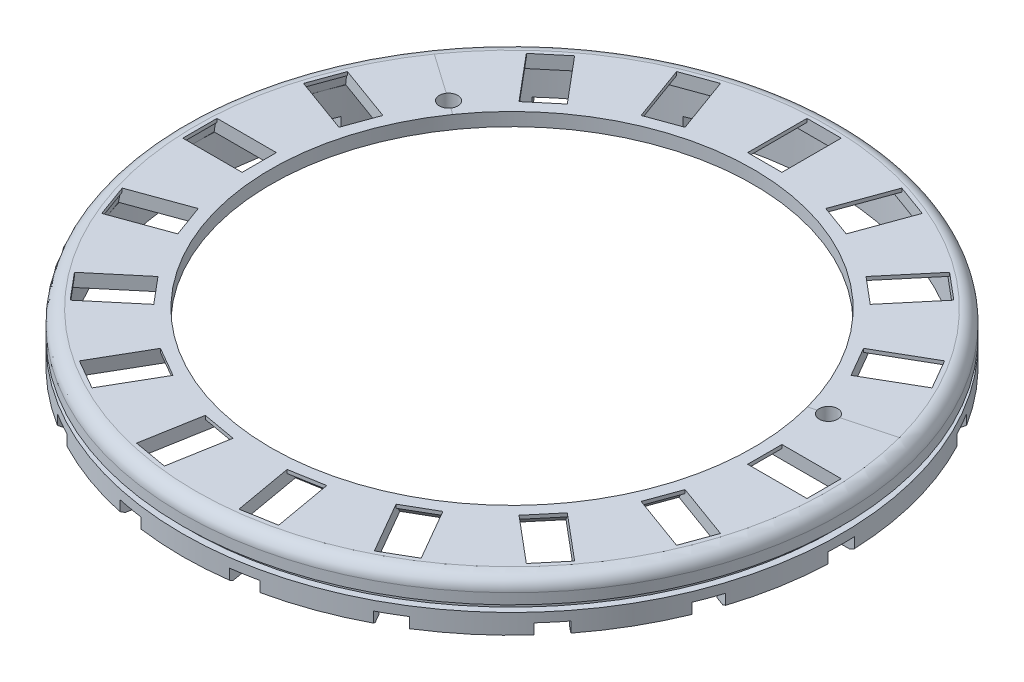
SolidWorks part; units mm, degrees
ref_plane "Front Plane" through (0, 0, 0) normal (0, 0, 1) x (1, 0, 0)
ref_plane "Top Plane" through (0, 0, 0) normal (0, 1, 0) x (1, 0, 0)
ref_plane "Right Plane" through (0, 0, 0) normal (1, 0, 0) x (0, 0, -1)
sketch "Sketch1" plane through (0, 0, 0) normal (0, 1, 0) x (1, 0, 0)
  circle A0 centre (0, 0) radius 25
  dimension "D1" = 50
extrude "Boss-Extrude1" add sketch "Sketch1" along normal blind 4
sketch "Sketch4" plane through (0, 4, 0) normal (0, 1, 0) x (1, 0, 0)
  circle A0 centre (0, 0) radius 18.3
  dimension "D1" = 36.6
extrude "Cut-Extrude2" cut sketch "Sketch4" against normal through all
sketch "Sketch5" plane through (0, 0, 0) normal (0, 0, 1) x (1, 0, 0)
  line L0 (0, 0) -> (0, 4) construction
  line L1 (18.3, 4) -> (-18.3, 4) construction
  line L2 (25, 0) -> (25, 4) construction
  line L3 (25, 2.2) -> (24.5, 2.2)
  line L4 (25, 2.2) -> (25, 1.7)
  line L5 (25, 1.7) -> (24.5, 1.7)
  line L6 (24.5, 2.2) -> (24.5, 1.7)
  line L8 (25, 4) -> (-25, 4) construction
  dimension "D1" = 1.8
  dimension "D2" = 0.5
  dimension "D3" = 49
revolve "Cut-Revolve1" cut sketch "Sketch5" angle 360 about L0
sketch "Sketch2" plane through (0, 0, 0) normal (0, 1, 0) x (1, 0, 0)
  circle A0 centre (0, 0) radius 23.9
  dimension "D1" = 47.8
extrude "Cut-Extrude1" cut sketch "Sketch2" along normal offset from surface (3 mm away) 1 up to face at (0, 4, 18.3)
sketch "Sketch6" plane through (0, 0, 0) normal (0, 0, 1) x (1, 0, 0)
  line L0 (0, 0) -> (0, 4) construction
  line L1 (18.3, 4) -> (-18.3, 4) construction
  line L2 (-25, 0.2021) -> (-24.65, 0)
  line L3 (-25, 1.7) -> (-25, 0) construction
  line L4 (-25, 0) -> (25, 0) construction
  line L5 (-25, 0.2021) -> (-25, 0)
  line L6 (-25, 0) -> (-24.65, 0)
  dimension "D1" = 49.3
  dimension "D2" = 30
revolve "Cut-Revolve2" cut sketch "Sketch6" angle 360 about L0
sketch "Sketch7" plane through (0, 4, 0) normal (0, 1, 0) x (1, 0, 0)
  line L0 (0, 0) -> (25, 0) construction
  line L1 (0, 0) -> (0, 9.991) construction
  line L2 (19.175, 1.3) -> (23.675, 1.3)
  line L3 (23.675, 1.3) -> (23.675, -1.3)
  line L4 (19.175, -1.3) -> (23.675, -1.3)
  line L5 (19.175, 1.3) -> (19.175, -1.3)
  circle A0 centre (0, 0) radius 25 construction
  point P8 (19.175, 0)
  point P14 (0, 0)
  point P15 (22.6405, 6.9219)
  dimension "D2" = 4.5
  dimension "D1" = 47.35
  dimension "D3" = 2.6
extrude "Cut-Extrude4" cut sketch "Sketch7" against normal up to next
sketch "Sketch14" plane through (23.675, 0, 0) normal (1, 0, 0) x (0, 0, -1)
  line L0 (0, 0) -> (0, 1.6878) construction
  line L1 (-1, 1) -> (1, 1)
  line L2 (-1, 1) -> (-1, 0)
  line L3 (-1, 0) -> (1, 0)
  line L4 (1, 1) -> (1, 0)
  line L5 (0, 1.7) -> (0, 0.2021) construction
  line L6 (-24.65, 0) -> (24.65, 0) construction
  line L7 (25, 4) -> (-25, 4) construction
  dimension "D1" = 2
  dimension "D2" = 3
extrude "Cut-Extrude9" cut sketch "Sketch14" along normal up to next
pattern_circular "CirPattern3" count 11 every 20 about axis through (0, 4, 0) along (0, -1, 0) of "Cut-Extrude4", "Cut-Extrude9"
sketch "Sketch9" plane through (0, 4, 0) normal (0, 1, 0) x (1, 0, 0)
  line L0 (0, 0) -> (25, 0) construction
  line L1 (0, 0) -> (21.6506, 12.5) construction
  line L2 (19.8532, 12.9633) -> (21.1532, 10.7117)
  line L3 (15.956, 10.7133) -> (19.8532, 12.9633)
  line L4 (17.256, 8.4617) -> (21.1532, 10.7117)
  line L5 (-0.65, 1.1258) -> (21.0006, 13.6258) construction
  line L6 (15.956, 10.7133) -> (17.256, 8.4617)
  circle A1 centre (0, 0) radius 25 construction
  point P14 (0.65, -1.1258)
  point P16 (22.3006, 11.3742)
  dimension "D1" = 30
  dimension "D2" = 2.6
  dimension "D3" = 23.675
  dimension "D4" = 4.5
extrude "Cut-Extrude5" cut sketch "Sketch9" against normal up to next
sketch "Sketch15" plane through (20.5032, 0, -11.8375) normal (-0.866, 0, 0.5) x (0.5, 0, 0.866)
  line L0 (0, 0) -> (0, 4) construction
  line L1 (1.3, 4) -> (-1.3, 4) construction
  line L2 (25, 4) -> (-25, 4) construction
  line L3 (-1, 1) -> (1, 1)
  line L4 (-1, 1) -> (-1, 0)
  line L5 (-1, 0) -> (1, 0)
  line L6 (1, 1) -> (1, 0)
  dimension "D1" = 3
  dimension "D2" = 2
extrude "Cut-Extrude10" cut sketch "Sketch15" against normal up to next
sketch "Sketch16" plane through (16.606, 0, -9.5875) normal (0.866, 0, -0.5) x (-0.5, 0, -0.866)
  line L0 (0, 0) -> (0, 4.7339) construction
  line L1 (-3.1617, 0) -> (3.1617, 0) construction
  line L2 (0, 0.2021) -> (0, 0) construction
  line L3 (-1, 1) -> (1, 1) construction
  line L4 (-18.3, 3) -> (18.3, 3) construction
  line L5 (-2.3664, 3) -> (2.3664, 3)
  arc A0 (-2.3664, 3) -> (2.3664, 3) centre (0, 0.7) cw
  dimension "D1" = 3.3
  dimension "D2" = 0.3
extrude "Cut-Extrude11" cut sketch "Sketch16" along normal up to surface (4.5 mm away) up to face at (20.5032, 3.5, -11.8375)
pattern_circular "CirPattern4" count 6 every 20 about axis through (0, 4, 0) along (0, -1, 0) of "Cut-Extrude5", "Cut-Extrude10", "Cut-Extrude11" reverse direction yes
sketch "Sketch3" plane through (0, 0, 0) normal (0, 0, 1) x (1, 0, 0)
  line L0 (-23.9, 3) -> (-18.3, 3)
  line L1 (18.4, 3) -> (18.975, 3.7332)
  line L2 (-23.9, 3) -> (23.9, 3) construction
  line L3 (18.975, 3.7332) -> (23.775, 3.7332)
  line L4 (23.775, 3.7332) -> (23.9, 3)
  line L7 (18.4, 3) -> (23.9, 3)
  line L12 (23.675, 3) -> (23.675, 4) construction
  line L15 (17.256, 3.7332) -> (21.1532, 3.7332) construction
  line L16 (19.175, 3) -> (19.175, 4) construction
  line L17 (-18.3, 3) -> (18.3, 3) construction
  line L18 (-18.3, 3) -> (18.3, 3) construction
  dimension "D1" = 0.1
  dimension "D2" = 0.1
  dimension "D3" = 0.2
ref_plane "Plane1" through (0, 0, -21.175) normal (0, 0, -1) x (-1, 0, 0)
extrude "Cut-Extrude12" cut sketch "Sketch3" against normal up to vertex (1.3 mm away) and the other way up to vertex (1.3 mm away) contours L3 L4 L7 L1 up to point (19.175, 4, -1.3) other way up to point (19.175, 4, 1.3)
pattern_circular "CirPattern10" count 11 every 20 about axis through (0, 4, 0) along (0, -1, 0) of "Cut-Extrude12"
fillet "Fillet1" radius 1 1 edges at (0, 4, 25)
hole_wizard "Ø1.4 (1.4) Diameter Hole1" positions "Sketch19" profile "Sketch18" hole size "Ø1.4" standard "DIN" end condition up to next
sketch "Sketch19" plane through (0, 4, 0) normal (0, 1, 0) x (1, 0, 0)
  line L0 (0, 0) -> (18.3, 0) construction
  line L1 (0, 0) -> (18.9321, 5.0729) construction
  line L2 (0, 0) -> (-22.2472, 8.0973) construction
  line L3 (-21.8026, 9.3189) -> (-22.6918, 6.8757) construction
  line L4 (0, 0) -> (-16.0554, 11.2421) construction
  circle A0 centre (0, 0) radius 19.6 construction
  circle A1 centre (0, 0) radius 18.3 construction
  point P15 (18.9321, 5.0729)
  point P27 (-16.0554, 11.2421)
  dimension "D1" = 39.2
  dimension "D2" = 15
  dimension "D3" = 35
sketch "Sketch18" plane through (18.9321, 4, -5.0729) normal (1, 0, 0) x (0, 0, 1)
  line L0 (0, 0) -> (0, 1)
  line L1 (0, 1) -> (0.7, 1)
  line L2 (0.7, 1) -> (0.7, 0)
  line L5 (0.7, 0) -> (0, 0)
  line L11 (0, -6.35) -> (0, 107.95) construction
  dimension "Thru Hole Dia." = 1.4
  dimension "Thru Hole Depth" = 1
sketch "Sketch21" plane through (0, 4, 0) normal (0, 1, 0) x (1, 0, 0)
  line L0 (0, 0) -> (25, 0) construction
  line L1 (-14.9905, 10.4964) -> (-20.4788, 14.3394)
  line L2 (17.6764, 4.7364) -> (24.1481, 6.4705)
  line L3 (-14.9905, 10.4964) -> (0, 0) construction
  line L4 (0, 0) -> (17.6764, 4.7364) construction
  circle A0 centre (0, 0) radius 25 construction
  arc A1 (-20.4788, 14.3394) -> (24.1481, 6.4705) centre (0, 0) ccw
  circle A2 centre (0, 0) radius 18.3 construction
  arc A3 (-14.9905, 10.4964) -> (17.6764, 4.7364) centre (0, 0) ccw
  dimension "D1" = 35
  dimension "D2" = 15
wrap "Wrap2" sketch "Sketch21" wrap type scribe source sketch "Sketch21" face at (18.9321, 4, -4.3729)
